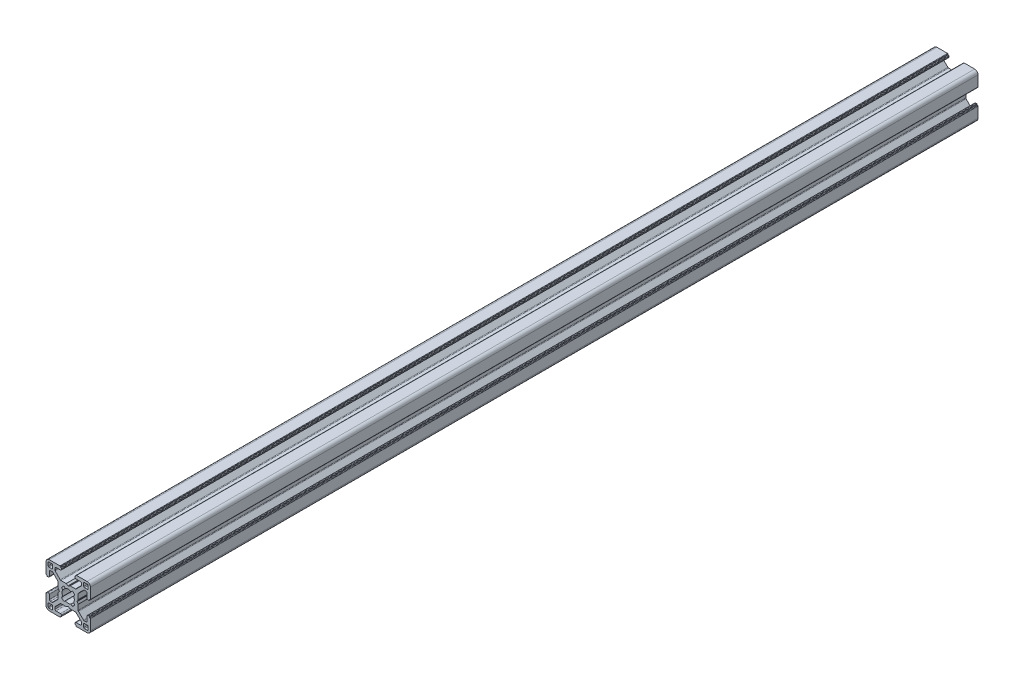
SolidWorks part; units mm, degrees
material "6063-O, Barra estrusa (SS)"
ref_plane "Piano frontale" through (0, 0, 0) normal (0, 0, 1) x (1, 0, 0)
ref_plane "Piano superiore" through (0, 0, 0) normal (0, 1, 0) x (1, 0, 0)
ref_plane "Piano destro" through (0, 0, 0) normal (1, 0, 0) x (0, 0, -1)
ref_plane "Piano1" through (0, 0, 100) normal (0, 0, 1) x (1, 0, 0)
sketch "Schizzo1" plane through (0, 0, 100) normal (0, 0, 1) x (1, 0, 0)
  line L0 (-1.9139, 2.9896) -> (-1.2582, 2.4453)
  line L1 (1.2582, 2.4453) -> (1.9139, 2.9896)
  line L2 (2.9922, 1.9099) -> (2.4453, 1.2582)
  line L3 (2.4453, -1.2582) -> (2.9922, -1.9099)
  line L4 (1.9139, -2.9896) -> (1.2582, -2.4453)
  line L5 (-1.2582, -2.4453) -> (-1.9139, -2.9896)
  line L6 (-2.9922, -1.9099) -> (-2.4453, -1.2582)
  line L7 (-2.4453, 1.2582) -> (-2.9922, 1.9099)
  line L8 (-9.3, 3) -> (-9, 3)
  line L9 (-8.5, 3.5) -> (-8.5, 5.5)
  line L10 (-8, 6) -> (-7.2678, 6)
  line L11 (-6.9142, 5.8536) -> (-4.6464, 3.5858)
  line L12 (-4.5, 3.2322) -> (-4.5, 0.9536)
  line L13 (-4.4732, 0.8536) -> (-4.0381, 0.1)
  line L14 (-4.0381, -0.1) -> (-4.4732, -0.8536)
  line L15 (-4.5, -0.9536) -> (-4.5, -3.2322)
  line L16 (-4.6464, -3.5858) -> (-6.9142, -5.8536)
  line L17 (-7.2678, -6) -> (-8, -6)
  line L18 (-8.5, -5.5) -> (-8.5, -3.5)
  line L19 (-9, -3) -> (-9.3, -3)
  line L20 (-9.5, -3.2) -> (-9.5, -3.35)
  line L21 (-9.7, -3.55) -> (-9.8, -3.55)
  line L22 (-10, -3.75) -> (-10, -8.5)
  line L23 (-8.5, -10) -> (-3.75, -10)
  line L24 (-3.55, -9.8) -> (-3.55, -9.7)
  line L25 (-3.35, -9.5) -> (-3.2, -9.5)
  line L26 (-3, -9.3) -> (-3, -9)
  line L27 (-3.5, -8.5) -> (-5.5, -8.5)
  line L28 (-6, -8) -> (-6, -7.2678)
  line L29 (-5.8536, -6.9142) -> (-3.5858, -4.6464)
  line L30 (-3.2322, -4.5) -> (-0.9536, -4.5)
  line L31 (-0.8536, -4.4732) -> (-0.1, -4.0381)
  line L32 (0.1, -4.0381) -> (0.8536, -4.4732)
  line L33 (0.9536, -4.5) -> (3.2322, -4.5)
  line L34 (3.5858, -4.6464) -> (5.8536, -6.9142)
  line L35 (6, -7.2678) -> (6, -8)
  line L36 (5.5, -8.5) -> (3.5, -8.5)
  line L37 (3, -9) -> (3, -9.3)
  line L38 (3.2, -9.5) -> (3.35, -9.5)
  line L39 (3.55, -9.7) -> (3.55, -9.8)
  line L40 (3.75, -10) -> (8.5, -10)
  line L41 (10, -8.5) -> (10, -3.75)
  line L42 (9.8, -3.55) -> (9.7, -3.55)
  line L43 (9.5, -3.35) -> (9.5, -3.2)
  line L44 (9.3, -3) -> (9, -3)
  line L45 (8.5, -3.5) -> (8.5, -5.5)
  line L46 (8, -6) -> (7.2678, -6)
  line L47 (6.9142, -5.8536) -> (4.6464, -3.5858)
  line L48 (4.5, -3.2322) -> (4.5, -0.9536)
  line L49 (4.4732, -0.8536) -> (4.0381, -0.1)
  line L50 (4.0381, 0.1) -> (4.4732, 0.8536)
  line L51 (4.5, 0.9536) -> (4.5, 3.2322)
  line L52 (4.6464, 3.5858) -> (6.9142, 5.8536)
  line L53 (7.2678, 6) -> (8, 6)
  line L54 (8.5, 5.5) -> (8.5, 3.5)
  line L55 (9, 3) -> (9.3, 3)
  line L56 (9.5, 3.2) -> (9.5, 3.35)
  line L57 (9.7, 3.55) -> (9.8, 3.55)
  line L58 (10, 3.75) -> (10, 8.5)
  line L59 (8.5, 10) -> (3.75, 10)
  line L60 (3.55, 9.8) -> (3.55, 9.7)
  line L61 (3.35, 9.5) -> (3.2, 9.5)
  line L62 (3, 9.3) -> (3, 9)
  line L63 (3.5, 8.5) -> (5.5, 8.5)
  line L64 (6, 8) -> (6, 7.2678)
  line L65 (5.8536, 6.9142) -> (3.5858, 4.6464)
  line L66 (3.2322, 4.5) -> (0.9536, 4.5)
  line L67 (0.8536, 4.4732) -> (0.1, 4.0381)
  line L68 (-0.1, 4.0381) -> (-0.8536, 4.4732)
  line L69 (-0.9536, 4.5) -> (-3.2322, 4.5)
  line L70 (-3.5858, 4.6464) -> (-5.8536, 6.9142)
  line L71 (-6, 7.2678) -> (-6, 8)
  line L72 (-5.5, 8.5) -> (-3.5, 8.5)
  line L73 (-3, 9) -> (-3, 9.3)
  line L74 (-3.2, 9.5) -> (-3.35, 9.5)
  line L75 (-3.55, 9.7) -> (-3.55, 9.8)
  line L76 (-3.75, 10) -> (-8.5, 10)
  line L77 (-10, 8.5) -> (-10, 3.75)
  line L78 (-9.8, 3.55) -> (-9.7, 3.55)
  line L79 (-9.5, 3.35) -> (-9.5, 3.2)
  line L80 (8.7, 7) -> (7.3, 7)
  line L81 (-7.3, 7) -> (-8.7, 7)
  line L82 (-7, 7.3) -> (-7, 8.7)
  line L83 (-7.3, 9) -> (-8.7, 9)
  line L84 (-9, 7.3) -> (-9, 8.7)
  line L85 (9, 7.3) -> (9, 8.7)
  line L86 (8.7, 9) -> (7.3, 9)
  line L87 (7, 7.3) -> (7, 8.7)
  line L88 (8.7, -9) -> (7.3, -9)
  line L89 (9, -8.7) -> (9, -7.3)
  line L90 (8.7, -7) -> (7.3, -7)
  line L91 (7, -8.7) -> (7, -7.3)
  line L92 (-7.3, -9) -> (-8.7, -9)
  line L93 (-7, -8.7) -> (-7, -7.3)
  line L94 (-7.3, -7) -> (-8.7, -7)
  line L95 (-9, -8.7) -> (-9, -7.3)
  arc A0 (-1.2582, 2.4453) -> (1.2582, 2.4453) centre (0, 0) cw
  arc A1 (1.9139, 2.9896) -> (2.9922, 1.9099) centre (0, 0) cw
  arc A2 (2.4453, 1.2582) -> (2.4453, -1.2582) centre (0, 0) cw
  arc A3 (2.9922, -1.9099) -> (1.9139, -2.9896) centre (0, 0) cw
  arc A4 (1.2582, -2.4453) -> (-1.2582, -2.4453) centre (0, 0) cw
  arc A5 (-1.9139, -2.9896) -> (-2.9922, -1.9099) centre (0, 0) cw
  arc A6 (-2.4453, -1.2582) -> (-2.4453, 1.2582) centre (0, 0) cw
  arc A7 (-2.9922, 1.9099) -> (-1.9139, 2.9896) centre (0, 0) cw
  arc A8 (-9.5, 3.2) -> (-9.3, 3) centre (-9.3, 3.2) ccw
  arc A9 (-9, 3) -> (-8.5, 3.5) centre (-9, 3.5) ccw
  arc A10 (-8.5, 5.5) -> (-8, 6) centre (-8, 5.5) cw
  arc A11 (-7.2678, 6) -> (-6.9142, 5.8536) centre (-7.2678, 5.5) cw
  arc A12 (-4.6464, 3.5858) -> (-4.5, 3.2322) centre (-5, 3.2322) cw
  arc A13 (-4.5, 0.9536) -> (-4.4732, 0.8536) centre (-4.3, 0.9536) ccw
  arc A14 (-4.0381, 0.1) -> (-4.0381, -0.1) centre (-4.2113, 0) cw
  arc A15 (-4.4732, -0.8536) -> (-4.5, -0.9536) centre (-4.3, -0.9536) ccw
  arc A16 (-4.5, -3.2322) -> (-4.6464, -3.5858) centre (-5, -3.2322) cw
  arc A17 (-6.9142, -5.8536) -> (-7.2678, -6) centre (-7.2678, -5.5) cw
  arc A18 (-8, -6) -> (-8.5, -5.5) centre (-8, -5.5) cw
  arc A19 (-8.5, -3.5) -> (-9, -3) centre (-9, -3.5) ccw
  arc A20 (-9.3, -3) -> (-9.5, -3.2) centre (-9.3, -3.2) ccw
  arc A21 (-9.5, -3.35) -> (-9.7, -3.55) centre (-9.7, -3.35) cw
  arc A22 (-9.8, -3.55) -> (-10, -3.75) centre (-9.8, -3.75) ccw
  arc A23 (-10, -8.5) -> (-8.5, -10) centre (-8.5, -8.5) ccw
  arc A24 (-3.75, -10) -> (-3.55, -9.8) centre (-3.75, -9.8) ccw
  arc A25 (-3.55, -9.7) -> (-3.35, -9.5) centre (-3.35, -9.7) cw
  arc A26 (-3.2, -9.5) -> (-3, -9.3) centre (-3.2, -9.3) ccw
  arc A27 (-3, -9) -> (-3.5, -8.5) centre (-3.5, -9) ccw
  arc A28 (-5.5, -8.5) -> (-6, -8) centre (-5.5, -8) cw
  arc A29 (-6, -7.2678) -> (-5.8536, -6.9142) centre (-5.5, -7.2678) cw
  arc A30 (-3.5858, -4.6464) -> (-3.2322, -4.5) centre (-3.2322, -5) cw
  arc A31 (-0.9536, -4.5) -> (-0.8536, -4.4732) centre (-0.9536, -4.3) ccw
  arc A32 (-0.1, -4.0381) -> (0.1, -4.0381) centre (0, -4.2113) cw
  arc A33 (0.8536, -4.4732) -> (0.9536, -4.5) centre (0.9536, -4.3) ccw
  arc A34 (3.2322, -4.5) -> (3.5858, -4.6464) centre (3.2322, -5) cw
  arc A35 (5.8536, -6.9142) -> (6, -7.2678) centre (5.5, -7.2678) cw
  arc A36 (6, -8) -> (5.5, -8.5) centre (5.5, -8) cw
  arc A37 (3.5, -8.5) -> (3, -9) centre (3.5, -9) ccw
  arc A38 (3, -9.3) -> (3.2, -9.5) centre (3.2, -9.3) ccw
  arc A39 (3.35, -9.5) -> (3.55, -9.7) centre (3.35, -9.7) cw
  arc A40 (3.55, -9.8) -> (3.75, -10) centre (3.75, -9.8) ccw
  arc A41 (8.5, -10) -> (10, -8.5) centre (8.5, -8.5) ccw
  arc A42 (10, -3.75) -> (9.8, -3.55) centre (9.8, -3.75) ccw
  arc A43 (9.7, -3.55) -> (9.5, -3.35) centre (9.7, -3.35) cw
  arc A44 (9.5, -3.2) -> (9.3, -3) centre (9.3, -3.2) ccw
  arc A45 (9, -3) -> (8.5, -3.5) centre (9, -3.5) ccw
  arc A46 (8.5, -5.5) -> (8, -6) centre (8, -5.5) cw
  arc A47 (7.2678, -6) -> (6.9142, -5.8536) centre (7.2678, -5.5) cw
  arc A48 (4.6464, -3.5858) -> (4.5, -3.2322) centre (5, -3.2322) cw
  arc A49 (4.5, -0.9536) -> (4.4732, -0.8536) centre (4.3, -0.9536) ccw
  arc A50 (4.0381, -0.1) -> (4.0381, 0.1) centre (4.2113, 0) cw
  arc A51 (4.4732, 0.8536) -> (4.5, 0.9536) centre (4.3, 0.9536) ccw
  arc A52 (4.5, 3.2322) -> (4.6464, 3.5858) centre (5, 3.2322) cw
  arc A53 (6.9142, 5.8536) -> (7.2678, 6) centre (7.2678, 5.5) cw
  arc A54 (8, 6) -> (8.5, 5.5) centre (8, 5.5) cw
  arc A55 (8.5, 3.5) -> (9, 3) centre (9, 3.5) ccw
  arc A56 (9.3, 3) -> (9.5, 3.2) centre (9.3, 3.2) ccw
  arc A57 (9.5, 3.35) -> (9.7, 3.55) centre (9.7, 3.35) cw
  arc A58 (9.8, 3.55) -> (10, 3.75) centre (9.8, 3.75) ccw
  arc A59 (10, 8.5) -> (8.5, 10) centre (8.5, 8.5) ccw
  arc A60 (3.75, 10) -> (3.55, 9.8) centre (3.75, 9.8) ccw
  arc A61 (3.55, 9.7) -> (3.35, 9.5) centre (3.35, 9.7) cw
  arc A62 (3.2, 9.5) -> (3, 9.3) centre (3.2, 9.3) ccw
  arc A63 (3, 9) -> (3.5, 8.5) centre (3.5, 9) ccw
  arc A64 (5.5, 8.5) -> (6, 8) centre (5.5, 8) cw
  arc A65 (6, 7.2678) -> (5.8536, 6.9142) centre (5.5, 7.2678) cw
  arc A66 (3.5858, 4.6464) -> (3.2322, 4.5) centre (3.2322, 5) cw
  arc A67 (0.9536, 4.5) -> (0.8536, 4.4732) centre (0.9536, 4.3) ccw
  arc A68 (0.1, 4.0381) -> (-0.1, 4.0381) centre (0, 4.2113) cw
  arc A69 (-0.8536, 4.4732) -> (-0.9536, 4.5) centre (-0.9536, 4.3) ccw
  arc A70 (-3.2322, 4.5) -> (-3.5858, 4.6464) centre (-3.2322, 5) cw
  arc A71 (-5.8536, 6.9142) -> (-6, 7.2678) centre (-5.5, 7.2678) cw
  arc A72 (-6, 8) -> (-5.5, 8.5) centre (-5.5, 8) cw
  arc A73 (-3.5, 8.5) -> (-3, 9) centre (-3.5, 9) ccw
  arc A74 (-3, 9.3) -> (-3.2, 9.5) centre (-3.2, 9.3) ccw
  arc A75 (-3.35, 9.5) -> (-3.55, 9.7) centre (-3.35, 9.7) cw
  arc A76 (-3.55, 9.8) -> (-3.75, 10) centre (-3.75, 9.8) ccw
  arc A77 (-8.5, 10) -> (-10, 8.5) centre (-8.5, 8.5) ccw
  arc A78 (-10, 3.75) -> (-9.8, 3.55) centre (-9.8, 3.75) ccw
  arc A79 (-9.7, 3.55) -> (-9.5, 3.35) centre (-9.7, 3.35) cw
  arc A80 (-8.7, 7) -> (-9, 7.3) centre (-8.7, 7.3) cw
  arc A81 (-7, 8.7) -> (-7.3, 9) centre (-7.3, 8.7) ccw
  arc A82 (-7.3, 7) -> (-7, 7.3) centre (-7.3, 7.3) ccw
  arc A83 (-8.7, 9) -> (-9, 8.7) centre (-8.7, 8.7) ccw
  arc A84 (7.3, 7) -> (7, 7.3) centre (7.3, 7.3) cw
  arc A85 (9, 8.7) -> (8.7, 9) centre (8.7, 8.7) ccw
  arc A86 (8.7, 7) -> (9, 7.3) centre (8.7, 7.3) ccw
  arc A87 (7.3, 9) -> (7, 8.7) centre (7.3, 8.7) ccw
  arc A88 (7.3, -9) -> (7, -8.7) centre (7.3, -8.7) cw
  arc A89 (9, -7.3) -> (8.7, -7) centre (8.7, -7.3) ccw
  arc A90 (8.7, -9) -> (9, -8.7) centre (8.7, -8.7) ccw
  arc A91 (7.3, -7) -> (7, -7.3) centre (7.3, -7.3) ccw
  arc A92 (-8.7, -9) -> (-9, -8.7) centre (-8.7, -8.7) cw
  arc A93 (-7, -7.3) -> (-7.3, -7) centre (-7.3, -7.3) ccw
  arc A94 (-7.3, -9) -> (-7, -8.7) centre (-7.3, -8.7) ccw
  arc A95 (-8.7, -7) -> (-9, -7.3) centre (-8.7, -7.3) ccw
  dimension "D1" = 0.3
  dimension "D2" = 1
  dimension "D3" = 1
  dimension "D4" = 1
  dimension "D7" = 1
  dimension "D8" = 1
  dimension "D9" = 1
  dimension "D10" = 1
  dimension "D5" = 2
  dimension "D6" = 2
extrude "Estrusione-Estrusione1" add sketch "Schizzo1" against normal blind 400
